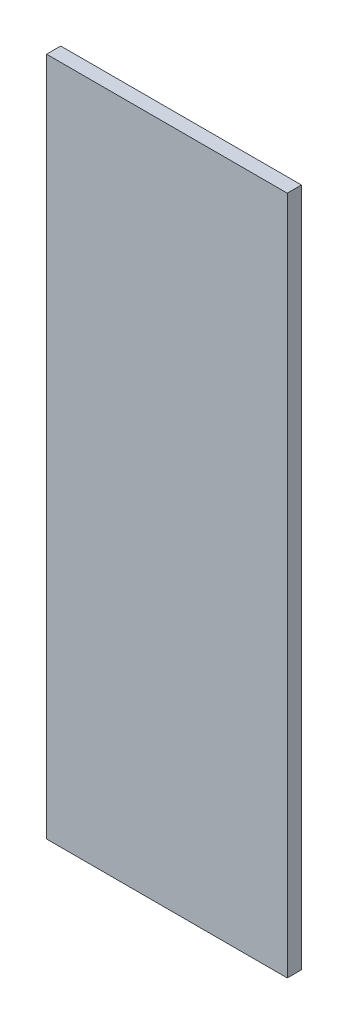
SolidWorks part; units mm, degrees
ref_plane "Front Plane" through (0, 0, 0) normal (0, 0, 1) x (1, 0, 0)
ref_plane "Top Plane" through (0, 0, 0) normal (0, 1, 0) x (1, 0, 0)
ref_plane "Right Plane" through (0, 0, 0) normal (1, 0, 0) x (0, 0, -1)
sketch "Sketch1" plane through (0, 0, 0) normal (0, 0, 1) x (1, 0, 0)
  line L1 (-53.975, 152.4) -> (53.975, 152.4)
  line L2 (-53.975, 152.4) -> (-53.975, -152.4)
  line L3 (-53.975, -152.4) -> (53.975, -152.4)
  line L4 (53.975, 152.4) -> (53.975, -152.4)
  line L5 (-53.975, 152.4) -> (53.975, -152.4) construction
  line L6 (-53.975, -152.4) -> (53.975, 152.4) construction
  point P0 (0, 0)
  dimension "D1" = 107.95
extrude "Boss-Extrude1" add sketch "Sketch1" along normal blind 6.35
